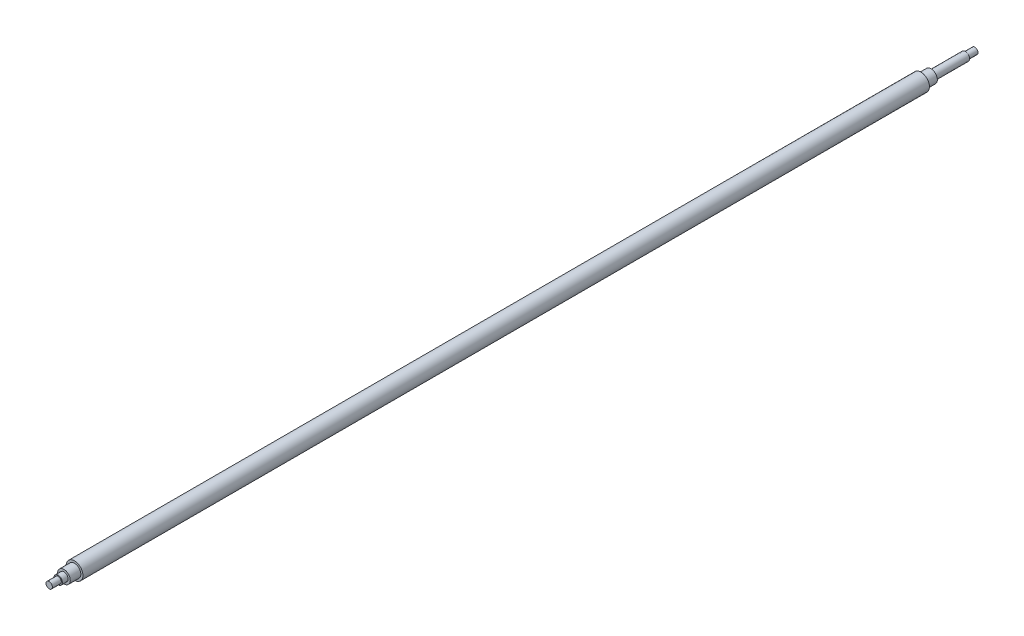
SolidWorks part; units mm, degrees
ref_plane "Piano frontale" through (0, 0, 0) normal (0, 0, 1) x (1, 0, 0)
ref_plane "Piano superiore" through (0, 0, 0) normal (0, 1, 0) x (1, 0, 0)
ref_plane "Piano destro" through (0, 0, 0) normal (1, 0, 0) x (0, 0, -1)
sketch "Schizzo2" plane through (0, 0, 0) normal (1, 0, 0) x (0, 0, -1)
  line L0 (0, 0) -> (0, 3)
  line L1 (0, 3) -> (8.5, 3)
  line L2 (8.5, 3) -> (8.5, 4)
  line L3 (8.5, 4) -> (14, 4)
  line L4 (14, 4) -> (14, 6)
  line L5 (14, 6) -> (24, 6)
  line L6 (24, 6) -> (24, 8)
  line L7 (24, 8) -> (826, 8)
  line L8 (826, 8) -> (826, 6)
  line L9 (826, 6) -> (835.5, 6)
  line L10 (835.5, 6) -> (835.5, 4)
  line L11 (877, 0) -> (0, 0)
  line L14 (877, 0) -> (877, 3)
  line L15 (0, 0) -> (351.0218, 0) construction
  line L16 (868, 3) -> (877, 3)
  line L17 (868, 4) -> (868, 3)
  line L18 (835.5, 4) -> (868, 4)
  point P33 (0, 0)
  dimension "D2" = 6
  dimension "D3" = 8
  dimension "D4" = 12
  dimension "D5" = 16
  dimension "D6" = 12
  dimension "D7" = 8
  dimension "D8" = 8.5
  dimension "D9" = 5.5
  dimension "D10" = 10
  dimension "D11" = 802
  dimension "D12" = 9.5
  dimension "D13" = 32.5
  dimension "D14" = 9
  dimension "D15" = 6
revolve "Rivoluzione2" add sketch "Schizzo2" angle 360 about L15
